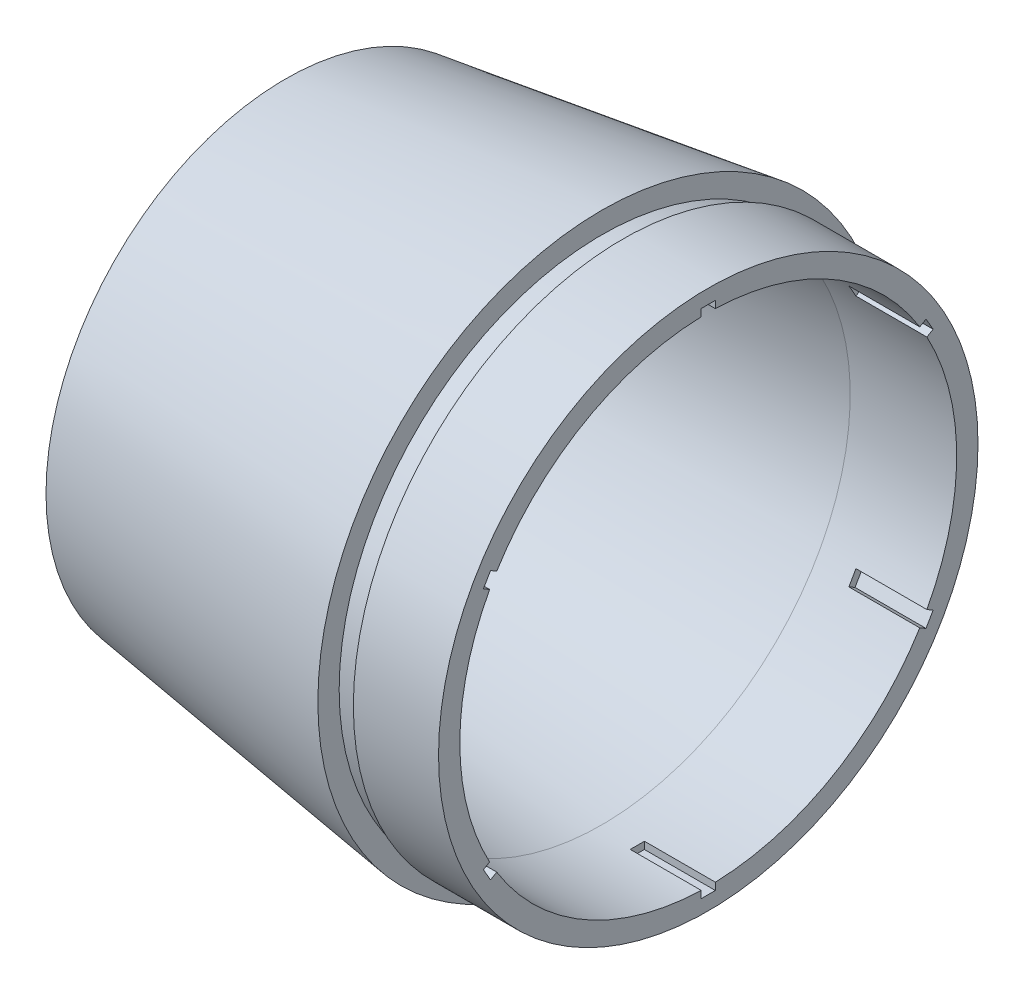
SolidWorks part; units mm, degrees
ref_plane "Ön Düzlem" through (0, 0, 0) normal (0, 0, 1) x (1, 0, 0)
ref_plane "Üst Düzlem" through (0, 0, 0) normal (0, 1, 0) x (1, 0, 0)
ref_plane "Sağ Düzlem" through (0, 0, 0) normal (1, 0, 0) x (0, 0, -1)
sketch "Çizim1" plane through (0, 0, 0) normal (0, 0, 1) x (1, 0, 0)
  line L0 (-44.5621, 33.7372) -> (-44.5621, 31.7372)
  line L1 (0, 40) -> (-44.5621, 33.7372)
  line L4 (-33.5551, 31.7372) -> (-44.5621, 31.7372)
  line L7 (-44.3163, 0) -> (0, 0)
  line L25 (-33.5551, 31.7372) -> (0, 35)
  line L27 (0, 35) -> (15, 35)
  line L28 (15, 35) -> (15, 38)
  line L29 (0, 40) -> (0, 37)
  line L30 (0, 37) -> (3, 37)
  line L31 (3, 37) -> (3, 38)
  line L32 (3, 38) -> (15, 38)
  dimension "D2" = 44.3163
ref_axis "Eksen1" through (0, 0, 0) along (-1, 0, 0)
revolve "Döndür2" add sketch "Çizim1" angle 360 about L7 region at (-14.4182, 35.4284, 0)
sketch "Çizim3" plane through (0, 0, 0) normal (0, 1, 0) x (1, 0, 0)
  line L1 (15, 1) -> (5, 1)
  line L10 (15, -1) -> (15, 1)
  line L13 (5, 1) -> (5, -1)
  line L14 (15, -1) -> (5, -1)
  line L15 (15, -38) -> (15, 38) construction
  point P2 (0, 0)
extrude "Kes-Ekstrüzyon1" cut sketch "Çizim3" against normal blind 36 contours L10 L1 L13 L14
pattern_circular "Dairesel Kaplama1" count 6 over 360 about axis through (0, 0, 0) along (-1, 0, 0) of "Kes-Ekstrüzyon1"
